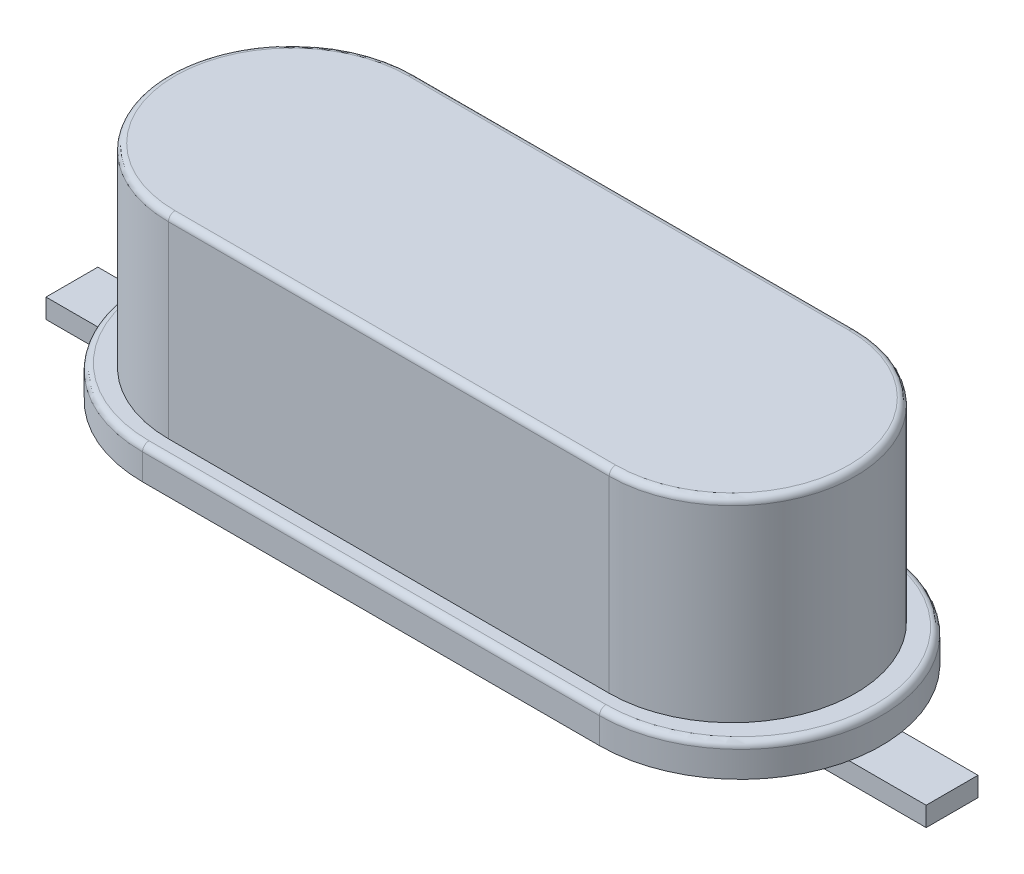
SolidWorks part; units mm, degrees
ref_plane "Front Plane" through (0, 0, 0) normal (0, 0, 1) x (1, 0, 0)
ref_plane "Top Plane" through (0, 0, 0) normal (0, 1, 0) x (1, 0, 0)
ref_plane "Right Plane" through (0, 0, 0) normal (1, 0, 0) x (0, 0, -1)
sketch "Sketch1" plane through (0, 0, 0) normal (0, 1, 0) x (1, 0, 0)
  line L0 (-3.525, 0) -> (3.525, 0) construction
  line L1 (-3.525, 2.175) -> (3.525, 2.175)
  line L2 (-3.525, -2.175) -> (3.525, -2.175)
  line L3 (-5.7, 0) -> (-5.7, 4.0267) construction
  line L4 (5.7, 0) -> (5.7, 3.7701) construction
  arc A0 (-3.525, 2.175) -> (-3.525, -2.175) centre (-3.525, 0) ccw
  arc A1 (3.525, -2.175) -> (3.525, 2.175) centre (3.525, 0) ccw
  point P2 (0, 0)
  dimension "D1" = 11.4
  dimension "D2" = 4.35
extrude "Boss-Extrude1" add sketch "Sketch1" along normal blind 0.5
fillet "Fillet1" radius 0.1 4 edges at (0, 0.5, -2.175) (5.7, 0.5, 0) (0, 0.5, 2.175) (-5.7, 0.5, 0)
sketch "Sketch2" plane through (0, 0.5, 0) normal (0, 1, 0) x (1, 0, 0)
  line L0 (-3.4, 0) -> (3.4, 0) construction
  line L1 (-3.4, 1.9) -> (3.4, 1.9)
  line L2 (-3.4, -1.9) -> (3.4, -1.9)
  line L3 (-5.3, 0) -> (-5.3, 3.8017) construction
  line L4 (5.3, 0) -> (5.3, 3.8017) construction
  arc A0 (-3.4, 1.9) -> (-3.4, -1.9) centre (-3.4, 0) ccw
  arc A1 (3.4, -1.9) -> (3.4, 1.9) centre (3.4, 0) ccw
  point P2 (0, 0)
  dimension "D1" = 3.8
  dimension "D2" = 10.6
extrude "Boss-Extrude2" add sketch "Sketch2" along normal blind 3
fillet "Fillet2" radius 0.1 4 edges at (0, 3.5, -1.9) (5.3, 3.5, 0) (0, 3.5, 1.9) (-5.3, 3.5, 0)
sketch "Sketch4" plane through (0, 0, 0) normal (0, -1, 0) x (1, 0, 0)
  line L0 (0, 0) -> (0, 3.708) construction
  line L1 (2.59, 0.4) -> (2.59, -0.4)
  line L2 (-2.59, 0.4) -> (-2.29, 0.4)
  line L3 (-2.59, 0.4) -> (-2.59, -0.4)
  line L4 (-2.59, -0.4) -> (-2.29, -0.4)
  line L5 (-2.29, 0.4) -> (-2.29, -0.4)
  line L6 (-2.59, 0.4) -> (-2.29, -0.4) construction
  line L7 (-2.59, -0.4) -> (-2.29, 0.4) construction
  line L8 (2.59, 0.4) -> (2.29, -0.4) construction
  line L9 (2.59, -0.4) -> (2.29, 0.4) construction
  line L10 (2.59, 0.4) -> (2.29, 0.4)
  line L11 (2.29, 0.4) -> (2.29, -0.4)
  line L12 (2.59, -0.4) -> (2.29, -0.4)
  point P3 (-2.44, 0)
  point P12 (2.44, 0)
  dimension "D1" = 0.8
  dimension "D2" = 0.3
  dimension "D3" = 2.44
extrude "Boss-Extrude3" add sketch "Sketch4" along normal blind 0.35
sketch "Sketch5" plane through (-2.59, 0, 0) normal (-1, 0, 0) x (0, 0, 1)
  line L0 (-0.4, -0.35) -> (-0.4, 0) construction
  line L1 (-0.4, -0.05) -> (0.4, -0.05)
  line L2 (-0.4, -0.05) -> (-0.4, -0.35)
  line L3 (-0.4, -0.35) -> (0.4, -0.35)
  line L4 (0.4, -0.05) -> (0.4, -0.35)
  dimension "D1" = 0.3
extrude "Boss-Extrude4" add sketch "Sketch5" along normal blind 4.2
mirror "Mirror1" about plane through (0, 0, 0) normal (1, 0, 0) of "Boss-Extrude4"
fillet "Fillet3" radius 0.2 4 edges at (2.29, -0.35, 0) (-2.29, -0.35, 0) (-2.59, -0.05, 0) (2.59, -0.05, 0)
